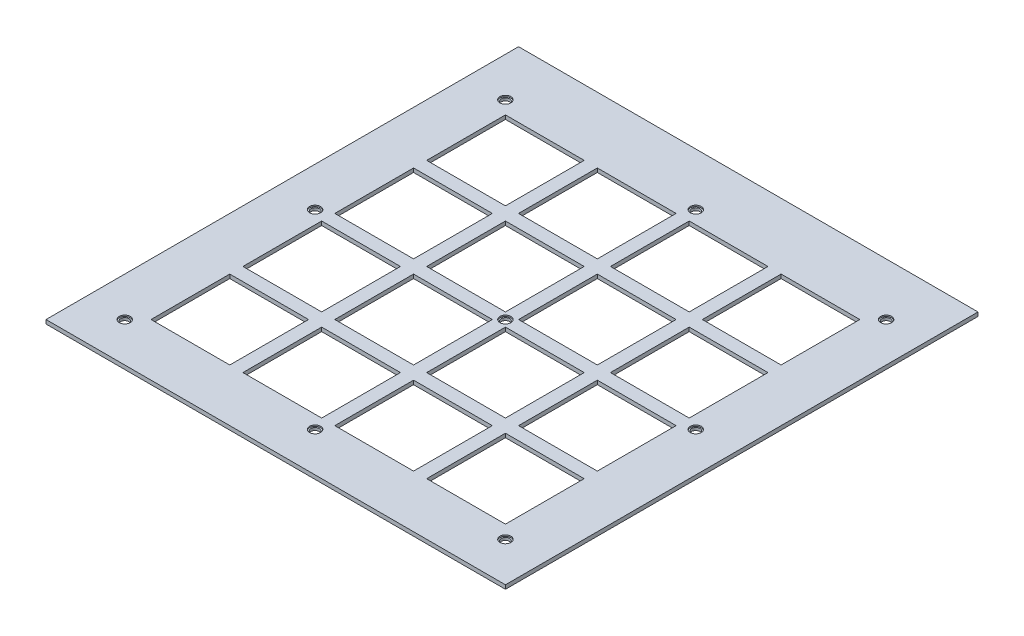
SolidWorks part; units mm, degrees
material "1.5714 (16NiCr4)"
ref_plane "Plan de face" through (0, 0, 0) normal (0, 0, 1) x (1, 0, 0)
ref_plane "Plan de dessus" through (0, 0, 0) normal (0, 1, 0) x (1, 0, 0)
ref_plane "Plan de droite" through (0, 0, 0) normal (1, 0, 0) x (0, 0, -1)
sketch "Esquisse1" plane through (0, 0, 0) normal (0, 1, 0) x (1, 0, 0)
  line L0 (290, 290) -> (310, 290) construction
  line L1 (20, 20) -> (20, 0) construction
  line L2 (20, 20) -> (80, 20)
  line L3 (80, 20) -> (80, 80)
  line L4 (80, 80) -> (20, 80)
  line L5 (20, 80) -> (20, 20)
  line L6 (290, 20) -> (290, 0) construction
  line L7 (85, 20) -> (85, 80) construction
  line L8 (20, 80) -> (20, 85) construction
  line L9 (20, 85) -> (75, 85) construction
  line L10 (20, 90) -> (20, 150)
  line L11 (80, 90) -> (20, 90)
  line L12 (80, 150) -> (80, 90)
  line L13 (20, 150) -> (80, 150)
  line L14 (20, 150) -> (20, 160) construction
  line L15 (20, 155) -> (156.6261, 155) construction
  line L16 (150, 80) -> (150, 85) construction
  line L17 (150, 150) -> (90, 150)
  line L18 (90, 150) -> (90, 90)
  line L19 (90, 90) -> (150, 90)
  line L20 (150, 90) -> (150, 150)
  line L21 (150, 80) -> (150, 20)
  line L22 (90, 80) -> (150, 80)
  line L23 (90, 20) -> (90, 80)
  line L24 (150, 20) -> (90, 20)
  line L25 (150, 80) -> (160, 80) construction
  line L26 (155, 80) -> (155, 40.4455) construction
  line L27 (160, 80) -> (160, 85) construction
  line L28 (290, 150) -> (290, 160) construction
  line L29 (290, 85) -> (235, 85) construction
  line L30 (290, 80) -> (290, 85) construction
  line L31 (225, 20) -> (225, 80) construction
  line L32 (160, 20) -> (220, 20)
  line L33 (220, 20) -> (220, 80)
  line L34 (220, 80) -> (160, 80)
  line L35 (160, 80) -> (160, 20)
  line L36 (160, 90) -> (160, 150)
  line L37 (220, 90) -> (160, 90)
  line L38 (220, 150) -> (220, 90)
  line L39 (160, 150) -> (220, 150)
  line L40 (290, 150) -> (230, 150)
  line L41 (230, 150) -> (230, 90)
  line L42 (230, 90) -> (290, 90)
  line L43 (290, 90) -> (290, 150)
  line L44 (20, 0) -> (0, 0) construction
  line L45 (290, 80) -> (290, 20)
  line L46 (230, 80) -> (290, 80)
  line L47 (230, 20) -> (230, 80)
  line L48 (290, 20) -> (230, 20)
  line L49 (225, 290) -> (225, 230) construction
  line L50 (290, 230) -> (290, 225) construction
  line L51 (290, 225) -> (235, 225) construction
  line L52 (160, 230) -> (160, 225) construction
  line L53 (155, 230) -> (155, 269.5545) construction
  line L54 (150, 230) -> (160, 230) construction
  line L55 (150, 230) -> (150, 225) construction
  line L56 (20, 225) -> (75, 225) construction
  line L57 (20, 230) -> (20, 225) construction
  line L58 (85, 290) -> (85, 230) construction
  line L59 (290, 290) -> (230, 290)
  line L60 (230, 290) -> (230, 230)
  line L61 (230, 230) -> (290, 230)
  line L62 (290, 230) -> (290, 290)
  line L63 (230, 290) -> (225, 290)
  line L64 (290, 220) -> (290, 160)
  line L65 (230, 220) -> (290, 220)
  line L66 (230, 160) -> (230, 220)
  line L67 (290, 160) -> (230, 160)
  line L68 (160, 160) -> (220, 160)
  line L69 (220, 160) -> (220, 220)
  line L70 (220, 220) -> (160, 220)
  line L71 (160, 220) -> (160, 160)
  line L72 (160, 230) -> (160, 290)
  line L73 (220, 230) -> (160, 230)
  line L74 (220, 290) -> (220, 230)
  line L75 (160, 290) -> (220, 290)
  line L76 (150, 290) -> (90, 290)
  line L77 (90, 290) -> (90, 230)
  line L78 (90, 230) -> (150, 230)
  line L79 (150, 230) -> (150, 290)
  line L80 (150, 220) -> (150, 160)
  line L81 (90, 220) -> (150, 220)
  line L82 (90, 160) -> (90, 220)
  line L83 (150, 160) -> (90, 160)
  line L84 (20, 160) -> (80, 160)
  line L85 (80, 160) -> (80, 220)
  line L86 (80, 220) -> (20, 220)
  line L87 (20, 220) -> (20, 160)
  line L88 (80, 290) -> (85, 290)
  line L89 (20, 230) -> (20, 290)
  line L90 (80, 230) -> (20, 230)
  line L91 (80, 290) -> (80, 230)
  line L92 (20, 290) -> (80, 290)
  line L93 (0, 0) -> (0, 310)
  line L94 (20, 290) -> (0, 290) construction
  line L95 (0, 310) -> (310, 310)
  line L96 (310, 0) -> (0, 0)
  line L97 (310, 310) -> (310, 0)
  line L98 (0, 310) -> (-20, 310) construction
  line L99 (0, 310) -> (0, 340) construction
  line L100 (310, 310) -> (330, 310) construction
  line L101 (0, 0) -> (0, -20) construction
  line L102 (-20, 340) -> (330, 340)
  line L103 (330, 340) -> (330, -20)
  line L104 (330, -20) -> (-20, -20)
  line L105 (-20, -20) -> (-20, 340)
  point P56 (290, 155)
  dimension "D1" = 60
  dimension "D2" = 60
  dimension "D3" = 60
  dimension "D4" = 60
  dimension "D5" = 60
  dimension "D6" = 60
  dimension "D7" = 60
  dimension "D8" = 60
  dimension "D9" = 270
  dimension "D10" = 270
  dimension "D11" = 20
  dimension "D12" = 20
  dimension "D13" = 20
  dimension "D14" = 20
  dimension "D15" = 20
  dimension "D16" = 30
  dimension "D17" = 20
  dimension "D18" = 20
  dimension "D19" = 20
extrude "Boss.-Extru.1" add sketch "Esquisse1" along normal blind 3 contours L97 L95 L93 L96 L80 L83 L82 L81 L79 L78 L77 L76 L64 L67 L66 L65 L62 L61 L60 L59 L36 L39 L38 L37 L35 L34 L33 L32 L10 L13 L12 L11 L5 L4 L3 L2 L20 L19 L18 L17 | L105 L104 L103 L102 L95 L97 L96 L93 region at (155, 0, -155) region at (155, 0, -334.979)
sketch "Esquisse2" plane through (0, 3, 0) normal (0, 1, 0) x (1, 0, 0)
  line L0 (0, 310) -> (20, 290) construction
  line L1 (20, 290) -> (80, 290) construction
  line L2 (310, 310) -> (290, 290) construction
  line L3 (20, 160) -> (20, 150) construction
  line L4 (160, 290) -> (150, 290) construction
  line L5 (155, 310) -> (155, 290) construction
  line L7 (155, 290) -> (155, 20) construction
  line L8 (20, 155) -> (0, 155) construction
  line L9 (155, 20) -> (155, 0) construction
  line L12 (290, 160) -> (290, 150) construction
  line L13 (290, 90) -> (290, 150) construction
  line L14 (290, 155) -> (310, 155) construction
  line L16 (0, 310) -> (310, 310) construction
  line L17 (310, 310) -> (310, 10) construction
  line L18 (0, 310) -> (0, 10) construction
  line L19 (0, 10) -> (310, 10) construction
  circle A0 centre (155, 300) radius 3.175
  circle A1 centre (10, 300) radius 3.175
  circle A2 centre (155, 155) radius 3.175
  circle A3 centre (300, 300) radius 3.175
  circle A4 centre (300, 155) radius 3.175
  circle A5 centre (10, 155) radius 3.175
  circle A6 centre (10, 10) radius 3.175
  circle A7 centre (300, 10) radius 3.175
  circle A8 centre (155, 10) radius 3.175
extrude "Enlèv. mat.-Extru.1" cut sketch "Esquisse2" against normal blind 5
extrude "Enlèv. de mat.-Extru.-Mince1" cut sketch "Esquisse2<2>" against normal blind 1 flip side to cut thin thin type one direction wall 1
sketch "Esquisse2<2>" plane through (0, 3, 0) normal (0, 1, 0) x (1, 0, 0) same geometry as "Esquisse2"
